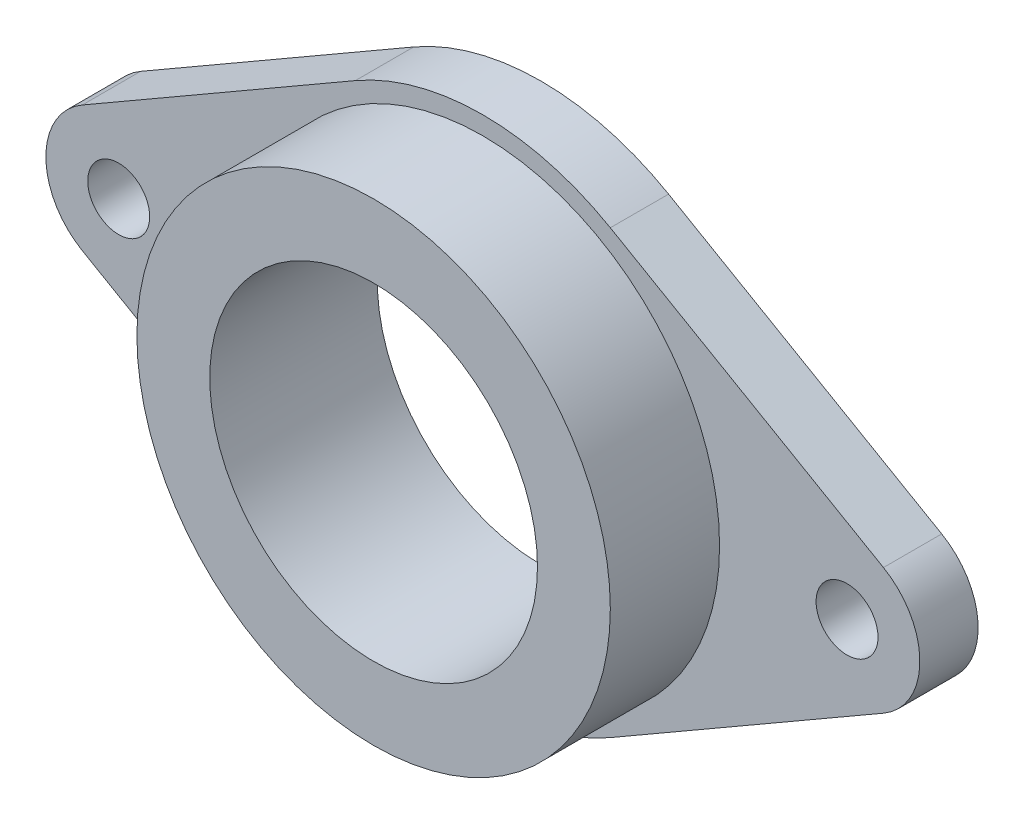
SolidWorks part; units mm, degrees
ref_plane "Front Plane" through (0, 0, 0) normal (0, 0, 1) x (1, 0, 0)
ref_plane "Top Plane" through (0, 0, 0) normal (0, 1, 0) x (1, 0, 0)
ref_plane "Right Plane" through (0, 0, 0) normal (1, 0, 0) x (0, 0, -1)
sketch "Sketch2" plane through (0, 0, 0) normal (0, 0, 1) x (1, 0, 0)
  line L0 (0, 0) -> (0, 15.494) construction
  line L1 (-50, 0) -> (0, 0) construction
  line L2 (-17.5, 30.3109) -> (-55, 8.6603)
  line L3 (-17.5, -30.3109) -> (-55, -8.6603)
  line L4 (17.5, -30.3109) -> (55, -8.6603)
  line L5 (17.5, 30.3109) -> (55, 8.6603)
  circle A0 centre (0, 0) radius 22.5
  circle A1 centre (0, 0) radius 32.5
  arc A2 (-17.5, -30.3109) -> (17.5, -30.3109) centre (0, 0) ccw
  arc A3 (-55, 8.6603) -> (-55, -8.6603) centre (-50, 0) ccw
  circle A4 centre (-50, 0) radius 4.25
  circle A5 centre (50, 0) radius 4.25
  arc A6 (55, 8.6603) -> (55, -8.6603) centre (50, 0) cw
  arc A7 (17.5, 30.3109) -> (-17.5, 30.3109) centre (0, 0) ccw
  dimension "D1" = 35
  dimension "D2" = 65
  dimension "D3" = 45
  dimension "D4" = 10
  dimension "D5" = 8.5
  dimension "D6" = 50
extrude "Boss-Extrude1" add sketch "Sketch2" along normal blind 8 contours L5 A7 L2 A3 L3 A2 L4 A6 A5 A4 A1 region at (0, 33.6108, 0)
extrude "Boss-Extrude2" add sketch "Sketch2<4>" along normal blind 23 contours A1 A0 region at (-31.5808, 0, 0)
sketch "Sketch2<4>" plane through (0, 0, 0) normal (0, 0, 1) x (1, 0, 0) same geometry as "Sketch2"
